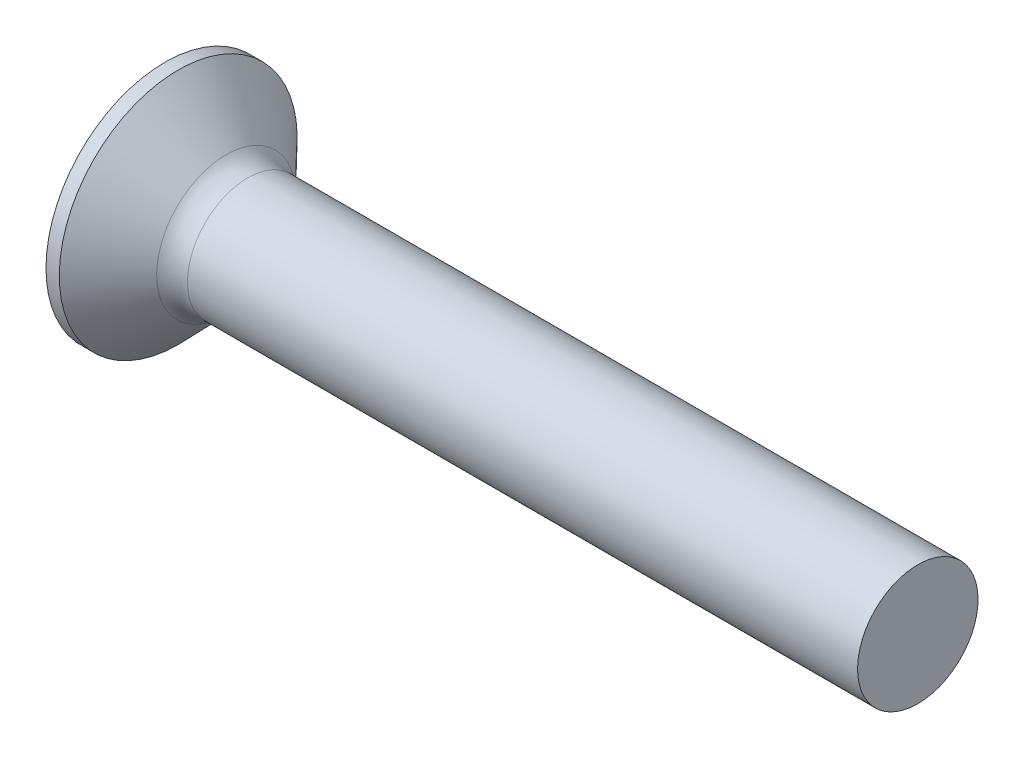
SolidWorks part; units mm, degrees
ref_plane "Front Plane" through (0, 0, 0) normal (0, 0, 1) x (1, 0, 0)
ref_plane "Top Plane" through (0, 0, 0) normal (0, 1, 0) x (1, 0, 0)
ref_plane "Right Plane" through (0, 0, 0) normal (1, 0, 0) x (0, 0, -1)
sketch "BodySke" plane through (0, 0, 0) normal (0, 0, 1) x (1, 0, 0)
  line L0 (2.0141, 0) -> (111.3824, 0) construction
  line L1 (2.0141, 0) -> (2.0141, 7.9) construction
  line L2 (2.0141, 7.9) -> (2.898, 7.9)
  line L3 (2.898, 7.9) -> (6.6641, 4)
  line L4 (6.6641, 4) -> (52.0141, 4)
  line L5 (52.0141, 4) -> (52.0141, 0)
  line L6 (7.9141, 1.8551) -> (7.9141, -12.8628) construction
  line L7 (2.0141, 0) -> (52.0141, 0)
  line L8 (9.1641, 2.7551) -> (9.1641, -11.0269) construction
  line L9 (2.0141, -7.9) -> (2.898, -7.9) construction
  line L10 (2.898, -7.9) -> (6.6641, -4) construction
  line L11 (6.6641, -4) -> (52.0141, -4) construction
  line L12 (2.0141, 0) -> (-7.747, 0) construction
  line L13 (0, 0) -> (0, 16.1338) construction
  line L14 (2.0141, 0) -> (0, 0)
  arc A0 (0, 0) -> (2.0141, 7.9) centre (16.5, 0) cw
  point P10 (52.0141, 3.4455)
  dimension "Thread_minor" = 6.891
  dimension "Length" = 50
  dimension "Head_height" = 4.65
  dimension "Head_dia" = 15.8
  dimension "Advance" = 1.25
revolve "BaseBody" add sketch "BodySke" angle 360 about L0
cosmetic thread "ThreadCosmetic" [suppressed] parameters "Thread_minor"=6.891
fillet "Fillet1" radius 2 1 edges at (6.6641, -4, 0)
ref_plane "Plane1" through (5.18, 0, 0) normal (1, 0, 0) x (0, 0, -1)
sketch "RecSkeTop" plane through (0, 0, 0) normal (1, 0, 0) x (0, 0, -1)
  line L1 (-0.946, 4.3) -> (0.946, 4.3)
  line L2 (-0.946, 4.3) -> (-0.946, -4.3)
  line L3 (-0.946, -4.3) -> (0.946, -4.3)
  line L4 (0.946, 4.3) -> (0.946, -4.3)
  dimension "D1" = 4.3
  dimension "D2" = 1.892
  dimension "D3" = 0.946
sketch "RecSkeBot" plane through (5.18, 0, 0) normal (1, 0, 0) x (0, 0, -1)
  line L0 (-0.946, 4.3) -> (-0.946, -4.3) construction
  line L1 (-0.946, 1.7173) -> (0.946, 1.7173)
  line L2 (-0.946, 1.7173) -> (-0.946, -1.7173)
  line L3 (-0.946, -1.7173) -> (0.946, -1.7173)
  line L4 (0.946, 1.7173) -> (0.946, -1.7173)
  line L5 (0.946, 4.3) -> (0.946, -4.3) construction
  dimension "D1" = 3.4347
  dimension "D2" = 1.7173
loft "Recess" cut profiles "RecSkeTop", "RecSkeBot" connector at (0, -4.3, 0.946) connector at (5.18, -1.7173, 0.946)
pattern_circular "RecPat" count 2 every 90 about axis through (2.0141, 0, 0) along (1, 0, 0) of "Recess"
sketch "RecCorSke" plane through (0, 0, 0) normal (0, 0, 1) x (1, 0, 0)
  line L0 (0, 0) -> (57.5987, 0) construction
  line L1 (0, 0) -> (0, 2.0812)
  line L3 (0, 2.0812) -> (5.18, 1.719)
  line L4 (5.18, 1.719) -> (5.7385, 0)
  line L5 (5.7385, 0) -> (0, 0)
  dimension "D1" = 18
  dimension "D2" = 5.18
  dimension "D3" = 2.0812
  dimension "D4" = 4
revolve "RecessCore" cut sketch "RecCorSke" angle 360 about L0
sketch "ThdSchSke" plane through (0, 0, 0) normal (0, 0, 1) x (1, 0, 0)
  line L0 (0, 0) -> (55.1256, 0) construction
  line L1 (2.0141, 0) -> (111.3824, 0) construction
  line L2 (51.694, 4) -> (51.694, 4.6403)
  line L3 (51.694, 4.6403) -> (52.3343, 4.6403)
  line L4 (52.3343, 4.6403) -> (52.3343, 4)
  line L5 (52.3343, 4) -> (52.0141, 3.4455)
  line L6 (52.0141, 3.4455) -> (51.694, 4)
  line L7 (6.6641, 4) -> (52.0141, 4) construction
  line L13 (52.0141, 4) -> (52.0141, 0) construction
revolve "ThreadSchematic" [suppressed] cut sketch "ThdSchSke" angle 360 about L0
pattern_linear "ThdSchPat" [suppressed] count 35 along (-1, 0, 0) of bodies 103
equation "\"Thread_minor@ThreadCosmetic\" = \"Thread_minor@BodySke\""
equation "\"D1@RecSkeTop\" = \"Cross_dia@RecSkeTop\" / 2"
equation "\"D2@RecSkeTop\" = \"Cross_dia@RecSkeTop\" * 0.22"
equation "\"D3@RecSkeTop\" = \"D2@RecSkeTop\" / 2"
equation "\"D1@RecSkeBot\" = \"Cross_dia@RecSkeTop\" - 2 * \"Cross_depth@Plane1\" *  tan( 26.5 * 0.017453292 ) "
equation "\"D2@RecSkeBot\" = \"D1@RecSkeBot\" / 2"
equation "\"D2@RecCorSke\" = \"Cross_depth@Plane1\""
equation "\"D3@RecCorSke\" = \"D2@RecSkeTop\" * 1.1"
equation "\"Advance@ThdSchPat\" = \"Advance@BodySke\""
equation "\"D1@ThdSchPat\" =  int(  ( \"Length@BodySke\"-\"Head_height@BodySke\"-\"Tread_runout@BodySke\" )  / \"Advance@ThdSchPat\" )  + 1"
